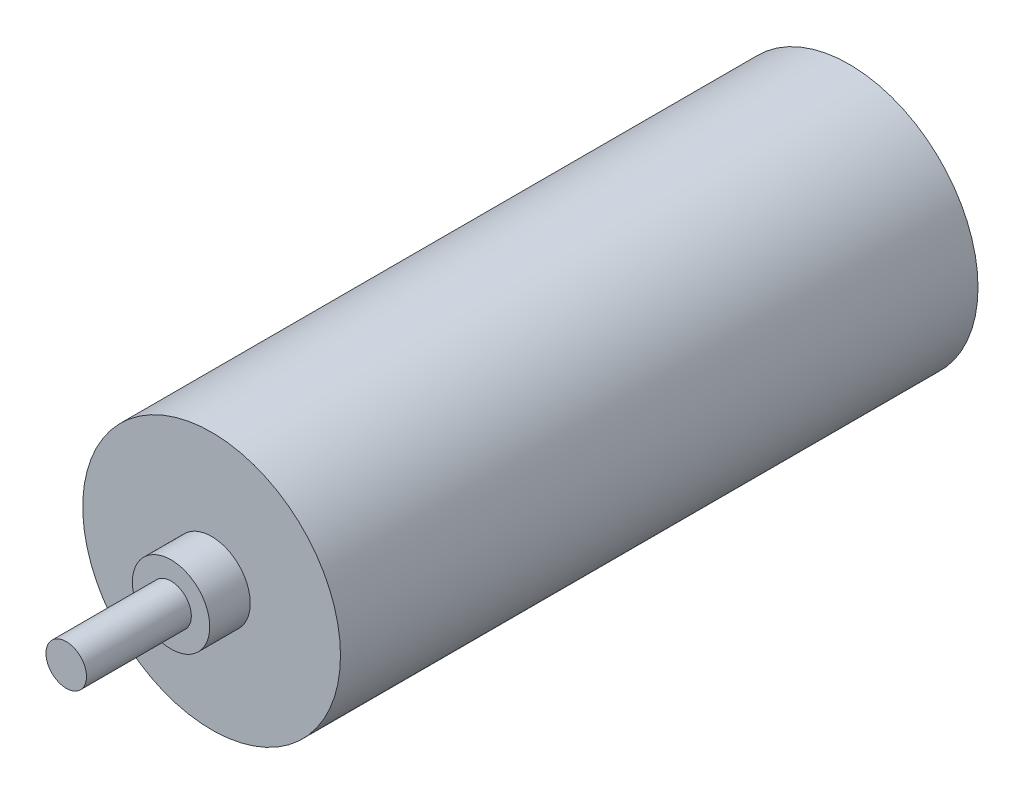
SolidWorks part; units mm, degrees
ref_plane "Front Plane" through (0, 0, 0) normal (0, 0, 1) x (1, 0, 0)
ref_plane "Top Plane" through (0, 0, 0) normal (0, 1, 0) x (1, 0, 0)
ref_plane "Right Plane" through (0, 0, 0) normal (1, 0, 0) x (0, 0, -1)
sketch "Sketch1" plane through (0, 0, 0) normal (0, 0, 1) x (1, 0, 0)
  circle A0 centre (0, 0) radius 19.05
  dimension "D1" = 38.1
extrude "Boss-Extrude1" add sketch "Sketch1" along normal blind 94.234
sketch "Sketch2" plane through (0, 0, 94.234) normal (0, 0, 1) x (1, 0, 0)
  circle A0 centre (0, 0) radius 5.715
  dimension "D1" = 11.43
extrude "Boss-Extrude2" add sketch "Sketch2" along normal blind 5.9944
sketch "Sketch3" plane through (0, 0, 100.2284) normal (0, 0, 1) x (1, 0, 0)
  circle A0 centre (0, 0) radius 2.9972
  dimension "D1" = 5.9944
extrude "Boss-Extrude3" add sketch "Sketch3" along normal blind 15.494
